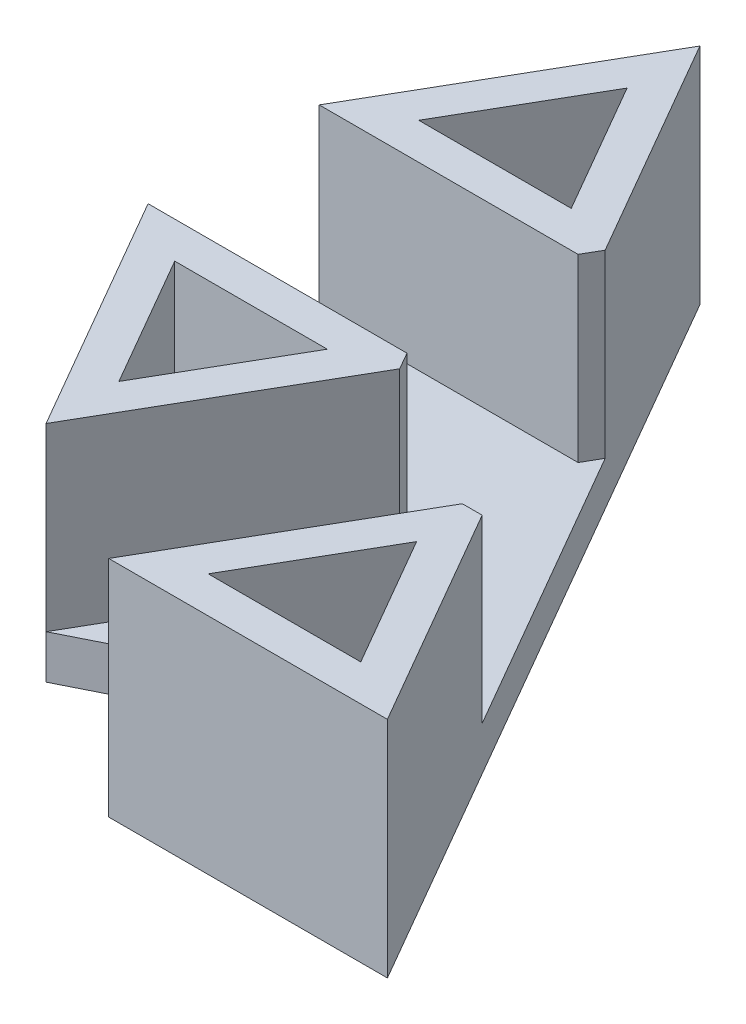
SolidWorks part; units mm, degrees
ref_plane "Front Plane" through (0, 0, 0) normal (0, 0, 1) x (1, 0, 0)
ref_plane "Top Plane" through (0, 0, 0) normal (0, 1, 0) x (1, 0, 0)
ref_plane "Right Plane" through (0, 0, 0) normal (1, 0, 0) x (0, 0, -1)
sketch "Sketch1" plane through (0, 0, 0) normal (0, 1, 0) x (1, 0, 0)
  line L186 (-130.0725, 0) -> (-118.5363, -19.9814)
  line L203 (-148.5263, -1.1782) -> (-139.6395, -7.0532)
  line L204 (-130.7528, -1.1782) -> (-148.5263, -1.1782)
  line L205 (-130.7528, -1.1782) -> (-130.0725, 0)
  line L206 (-144.1962, 1.3218) -> (-138.9593, 10.3923)
  line L207 (-138.9593, 10.3923) -> (-133.7224, 1.3218)
  line L208 (-144.1962, 1.3218) -> (-133.7224, 1.3218)
  line L209 (-138.9593, 15.3923) -> (-148.5263, -1.1782)
  line L210 (-138.9593, 15.3923) -> (-130.0725, 0)
  line L211 (-138.9593, -29.4987) -> (-130.0725, -14.1064)
  line L212 (-138.9593, -29.4987) -> (-148.5263, -12.9282)
  line L213 (-144.1962, -15.4282) -> (-133.7224, -15.4282)
  line L214 (-138.9593, -24.4987) -> (-133.7224, -15.4282)
  line L215 (-144.1962, -15.4282) -> (-138.9593, -24.4987)
  line L216 (-130.7528, -12.9282) -> (-130.0725, -14.1064)
  line L217 (-130.7528, -12.9282) -> (-148.5263, -12.9282)
  line L218 (-148.5263, -12.9282) -> (-139.6395, -7.0532)
  line L219 (-129.428, -24.7401) -> (-138.9593, -29.4987)
  line L228 (-129.428, -24.7401) -> (-128.7835, -35.3737)
  line L231 (-118.5363, -19.9814) -> (-109.6495, -35.3737)
  line L232 (-118.5363, -19.9814) -> (-119.8967, -19.9814)
  line L233 (-113.9796, -32.8737) -> (-124.4534, -32.8737)
  line L234 (-124.4534, -32.8737) -> (-119.2165, -23.8032)
  line L235 (-113.9796, -32.8737) -> (-119.2165, -23.8032)
  line L236 (-128.7835, -35.3737) -> (-109.6495, -35.3737)
  line L237 (-128.7835, -35.3737) -> (-119.8967, -19.9814)
extrude "Boss-Extrude3" add sketch "Sketch1" along normal blind 15.38 contours L210 L209 L204 L205 L208 L206 L207 | L216 L217 L212 L211 L215 L213 L214 | L237 L236 L231 L232 L235 L233 L234
extrude "Boss-Extrude5" add sketch "Sketch1<7>" along normal blind 3 contours L228 L237 L232 L231 L210 L205 L204 L203 L218 L217 L216 L211 L219 region at (-124.706, 0, 10.2226)
sketch "Sketch1<7>" plane through (0, 0, 0) normal (0, 1, 0) x (1, 0, 0) same geometry as "Sketch1"
